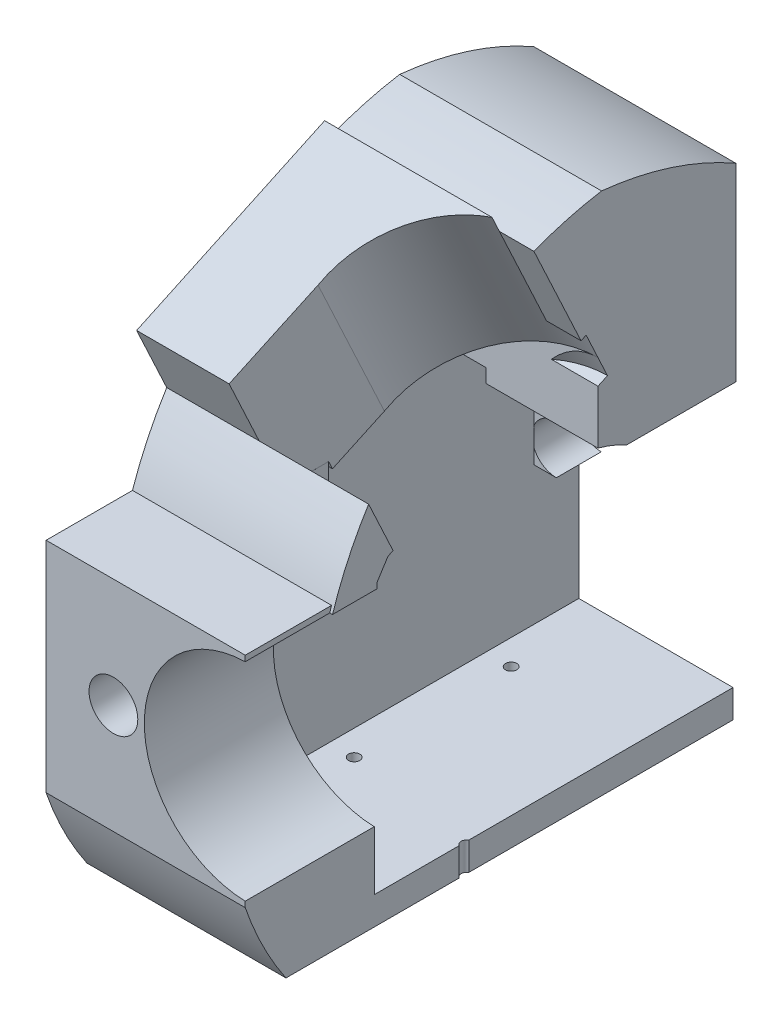
SolidWorks part; units mm, degrees
ref_plane "Front Plane" through (0, 0, 0) normal (0, 0, 1) x (1, 0, 0)
ref_plane "Top Plane" through (0, 0, 0) normal (0, 1, 0) x (1, 0, 0)
ref_plane "Right Plane" through (0, 0, 0) normal (1, 0, 0) x (0, 0, -1)
sketch "Sketch1" plane through (0, 0, 14.8713) normal (0, 0, 1) x (1, 0, 0)
  line L0 (17.8011, 32) -> (17.8011, 29.35)
  line L1 (13.8011, 20.65) -> (13.8011, 19.2554)
  line L2 (13.8011, 20.65) -> (13.8011, -4) construction
  line L3 (13.8011, 20.65) -> (17.8011, 20.65)
  arc A0 (17.8011, 32) -> (13.8011, 19.2554) centre (17.8011, 25) ccw
  arc A1 (22.3161, 30.3493) -> (17.8011, 32) centre (17.8011, 25) ccw construction
  arc A2 (17.8011, 29.35) -> (17.8011, 20.65) centre (17.8011, 25) ccw
extrude "Boss-Extrude1" add sketch "Sketch1" against normal up to surface (10.8581 mm away)
sketch "Sketch2" plane through (0, 0, -49.1287) normal (0, 0, -1) x (-1, 0, 0)
  line L0 (-13.8011, 19.2554) -> (-13.8011, 20.65)
  line L1 (-13.8011, 20.65) -> (-13.8011, -4) construction
  line L2 (-13.8011, 20.65) -> (-17.8011, 20.65)
  line L3 (-17.8011, 32) -> (-17.8011, 29.35)
  arc A0 (-13.8011, 19.2554) -> (-17.8011, 32) centre (-17.8011, 25) ccw
  arc A1 (-17.8011, 20.65) -> (-17.8011, 29.35) centre (-17.8011, 25) ccw
extrude "Boss-Extrude2" add sketch "Sketch2" against normal up to surface (8 mm away) separate body
sketch "Sketch3" plane through (0, 0, 14.8713) normal (0, 0, 1) x (1, 0, 0)
  line L0 (22.3161, 44.5) -> (61.3161, 44.5) construction
  line L1 (13.8011, 44.5) -> (5.8011, 44.5)
  line L3 (13.8011, -4) -> (5.8011, -4)
  line L4 (5.8011, 44.5) -> (5.8011, -4)
  line L5 (41.3161, -4) -> (13.8011, -4) construction
  line L6 (13.8011, 19.2554) -> (13.8011, -4)
  line L7 (22.3161, 30.3493) -> (22.3161, 44.5)
  line L8 (22.3161, 44.5) -> (13.8011, 44.5)
  arc A2 (22.3161, 30.3493) -> (17.8011, 32) centre (17.8011, 25) ccw construction
  arc A4 (22.3161, 30.3493) -> (17.8011, 32) centre (17.8011, 25) ccw
  arc A5 (17.8011, 32) -> (13.8011, 19.2554) centre (17.8011, 25) ccw construction
  arc A6 (17.8011, 32) -> (13.8011, 19.2554) centre (17.8011, 25) ccw
  dimension "D1" = 8
extrude "Boss-Extrude3" add sketch "Sketch3" against normal up to surface (10.8581 mm away)
sketch "Sketch4" plane through (0, 0, -49.1287) normal (0, 0, -1) x (-1, 0, 0)
  line L0 (-13.8011, 20.65) -> (-13.8011, -4) construction
  line L1 (-17.8011, 32) -> (-17.8011, 43.4634) construction
  line L2 (-13.8011, 19.2554) -> (-13.8011, -4)
  line L3 (-17.8011, 32) -> (-17.8011, 43.4634)
  line L4 (-17.8011, 43.4634) -> (-5.8011, 43.4634)
  line L5 (-5.8011, 44.5) -> (-5.8011, -4) construction
  line L6 (-5.8011, 43.4634) -> (-5.8011, -4)
  line L7 (-5.8011, -4) -> (-13.8011, -4)
  arc A0 (-13.8011, 19.2554) -> (-17.8011, 32) centre (-17.8011, 25) ccw construction
  arc A1 (-13.8011, 19.2554) -> (-17.8011, 32) centre (-17.8011, 25) ccw
extrude "Boss-Extrude4" add sketch "Sketch4" against normal up to surface (8 mm away)
sketch "Sketch5" plane through (0, 0, -41.1287) normal (0, 0, 1) x (1, 0, 0)
  line L2 (5.8011, 43.4634) -> (13.8011, 43.4634)
  line L3 (5.8011, 43.4634) -> (5.8011, -4)
  line L4 (5.8011, -4) -> (13.8011, -4)
  line L6 (13.8011, 43.4634) -> (13.8011, -4)
extrude "Boss-Extrude5" add sketch "Sketch5" along normal up to surface (45.1419 mm away) up to face at (14.7818, 23.8221, 4.0131)
sketch "Sketch6" plane through (0, 0, 14.8713) normal (0, 0, 1) x (1, 0, 0)
  line L0 (41.3161, 6.5068) -> (41.3161, -4)
  line L1 (5.8011, 44.5) -> (41.3161, 44.5)
  line L2 (5.8011, 44.5) -> (5.8011, -4)
  line L3 (5.8011, -4) -> (41.3161, -4)
  line L4 (41.3161, 44.5) -> (41.3161, 43.4932)
  circle A0 centre (41.8161, 25) radius 18.5 construction
  arc A1 (41.3161, 43.4932) -> (41.3161, 6.5068) centre (41.8161, 25) ccw
  arc A2 (17.8011, 20.65) -> (17.8011, 29.35) centre (17.8011, 25) ccw construction
  arc A3 (17.8011, 20.65) -> (17.8011, 29.35) centre (17.8011, 25) ccw
  arc A4 (17.8011, 29.35) -> (17.8011, 20.65) centre (17.8011, 25) ccw construction
  arc A5 (17.8011, 29.35) -> (17.8011, 20.65) centre (17.8011, 25) ccw
  point P8 (0, 0)
extrude "Boss-Extrude6" add sketch "Sketch6" along normal up to surface (23.0162 mm away)
sketch "Sketch7" plane through (41.8161, 0, 0) normal (-1, 0, 0) x (0, 0, 1)
  line L7 (16.3792, 57.333) -> (12.0176, 47.9794)
  line L8 (12.0176, 47.9794) -> (12.9239, 47.5568)
  line L9 (12.9239, 47.5568) -> (14.8713, 44.5)
  line L10 (14.8713, 44.5) -> (14.8713, 43.5)
  line L11 (14.8713, 43.5) -> (22.814, 43.5)
  line L13 (16.3792, 57.333) -> (12.0176, 47.9794)
  line L14 (12.0176, 47.9794) -> (12.9239, 47.5568)
  line L15 (12.9239, 47.5568) -> (14.8713, 44.5)
  line L16 (14.8713, 44.5) -> (14.8713, 43.5)
  line L17 (14.8713, 43.5) -> (22.814, 43.5)
  line L20 (-49.1287, 77.2293) -> (-49.1287, 43.4634)
  line L21 (-49.1287, 43.4634) -> (-24.5352, 43.4634)
  line L22 (-24.5352, 43.4634) -> (-24.5352, 59.5074)
  line L23 (-24.5352, 59.5074) -> (-22.4221, 64.0389)
  line L24 (-22.4221, 64.0389) -> (-21.5158, 63.6163)
  line L25 (-21.5158, 63.6163) -> (-13.1095, 81.6438)
  line L27 (-49.1287, 77.2293) -> (-49.1287, 43.4634)
  line L28 (-49.1287, 43.4634) -> (-29.5923, 43.4634)
  line L29 (-24.5352, 45.5265) -> (-24.5352, 59.5074)
  line L30 (-24.5352, 59.5074) -> (-22.4221, 64.0389)
  line L31 (-22.4221, 64.0389) -> (-21.5158, 63.6163)
  line L32 (-21.5158, 63.6163) -> (-13.1095, 81.6438)
  arc A0 (-24.5352, 45.5265) -> (-29.5923, 43.4634) centre (-19.1104, 25) ccw
  arc A1 (22.814, 43.5) -> (16.3792, 57.333) centre (-35.0418, 25) ccw
  arc A3 (-25.1762, 84.9351) -> (-49.1287, 77.2293) centre (-19.1104, 25) ccw
  arc A4 (-25.1762, 84.9351) -> (-49.1287, 77.2293) centre (-19.1104, 25) ccw
  arc A21 (22.814, 43.5) -> (16.3792, 57.333) centre (-35.0418, 25) ccw
  arc A23 (-13.1095, 81.6438) -> (-25.1762, 84.9351) centre (-35.0418, 25) ccw
  arc A24 (-13.1095, 81.6438) -> (-25.1762, 84.9351) centre (-35.0418, 25) ccw
  dimension "D1" = 0
  dimension "D2" = 0
extrude "Boss-Extrude7" add sketch "Sketch7" along normal up to surface (36.015 mm away) up to face at (5.8011, 27.9878, -2.4094)
sketch "Sketch8" plane through (5.8011, 0, 0) normal (-1, 0, 0) x (0, 0, 1)
  line L0 (14.8713, 44.5) -> (12.9239, 47.5568)
  line L1 (12.9239, 47.5568) -> (12.0176, 47.9794)
  line L2 (12.0176, 47.9794) -> (-24.5352, 47.9794)
  line L3 (-24.5352, 45.5265) -> (-24.5352, 59.5074) construction
  line L4 (-24.5352, 47.9794) -> (-24.5352, 45.5265)
  line L5 (-29.5923, 43.4634) -> (4.0131, 43.4634)
  line L6 (4.0131, 43.4634) -> (4.0131, 44.5)
  line L7 (4.0131, 44.5) -> (14.8713, 44.5)
  arc A0 (-24.5352, 45.5265) -> (-29.5923, 43.4634) centre (-19.1104, 25) ccw construction
  arc A1 (-24.5352, 45.5265) -> (-29.5923, 43.4634) centre (-19.1104, 25) ccw
extrude "Boss-Extrude8" add sketch "Sketch8" against normal up to surface (8 mm away) up to face at (13.8011, 23.4608, -18.9669)
sketch "Sketch9" plane through (13.8011, 0, 0) normal (1, 0, 0) x (0, 0, -1)
  line L0 (-4.0131, 44.5) -> (-4.0131, 47.9794)
  line L17 (-14.8713, 20.65) -> (-14.8713, -4)
  line L18 (-14.8713, -4) -> (49.1287, -4)
  line L19 (49.1287, -4) -> (49.1287, 20.65)
  line L20 (49.1287, 20.65) -> (41.1287, 20.65)
  line L21 (41.1287, 20.65) -> (41.1287, 23.2905)
  line L22 (41.1287, 23.2905) -> (41.1287, 26.7095)
  line L23 (41.1287, 26.7095) -> (41.1287, 43.4634)
  line L24 (41.1287, 43.4634) -> (29.5923, 43.4634)
  line L25 (24.5352, 45.5265) -> (24.5352, 47.9794)
  line L26 (24.5352, 47.9794) -> (-12.0176, 47.9794)
  line L27 (-12.0176, 47.9794) -> (-12.9239, 47.5568)
  line L28 (-12.9239, 47.5568) -> (-14.8713, 44.5)
  line L29 (-14.8713, 44.5) -> (-4.0131, 44.5)
  line L30 (-4.0131, 44.5) -> (-4.0131, 26.7095)
  line L31 (-4.0131, 26.7095) -> (-4.0131, 23.2905)
  line L32 (-4.0131, 23.2905) -> (-4.0131, 20.65)
  line L33 (-4.0131, 20.65) -> (-14.8713, 20.65)
  line L43 (-4.0131, 47.9794) -> (-12.0176, 47.9794)
  line L44 (-12.0176, 47.9794) -> (-12.9239, 47.5568)
  line L45 (-12.9239, 47.5568) -> (-14.8713, 44.5)
  line L46 (-14.8713, 44.5) -> (-4.0131, 44.5)
  arc A1 (29.5923, 43.4634) -> (24.5352, 45.5265) centre (19.1104, 25) ccw
  dimension "D1" = 0
extrude "Boss-Extrude9" add sketch "Sketch9" along normal up to surface (8.515 mm away)
sketch "Sketch11" plane through (13.8011, 0, 0) normal (1, 0, 0) x (0, 0, -1)
  line L0 (24.5352, 47.9794) -> (24.5352, 45.5265)
  line L1 (41.1287, 43.4634) -> (41.1287, 47.9794)
  line L2 (52.7432, 45.6866) -> (52.5609, 45.6856)
  line L3 (41.1287, 47.9794) -> (24.5352, 47.9794)
  line L4 (49.1287, 43.4634) -> (29.5923, 43.4634) construction
  line L5 (41.1287, 43.4634) -> (29.5923, 43.4634)
  arc A0 (29.5923, 43.4634) -> (24.5352, 45.5265) centre (19.1104, 25) ccw construction
  arc A1 (29.5923, 43.4634) -> (24.5352, 45.5265) centre (19.1104, 25) ccw
extrude "Cut-Extrude4" cut sketch "Sketch11" along normal blind 8 contours A1 L0 L3 L1 L5
sketch "Sketch14" plane through (0, 39.4814, 18.4105) normal (0, -0.9063, -0.4226) x (1, 0, 0)
  line L2 (22.3161, -16.6399) -> (13.8011, -16.6399)
  line L3 (13.8011, -16.6399) -> (13.8011, -44.7208)
  line L4 (13.8011, -44.7208) -> (31.9764, -44.7208)
  line L5 (22.3161, -16.6399) -> (22.3448, -26.8287)
  arc A0 (22.3448, -26.8287) -> (61.3161, -27.8854) centre (41.8161, -27.8854) ccw construction
  arc A1 (22.3448, -26.8287) -> (31.9764, -44.7208) centre (41.8161, -27.8854) ccw
extrude "Boss-Extrude19" add sketch "Sketch14" against normal up to surface (5 mm away) separate body
sketch "Sketch15" plane through (0, 20.0259, -42.9457) normal (0, -0.4226, 0.9063) x (1, 0, 0)
  line L4 (5.8011, 48.563) -> (5.8011, 43.563)
  line L5 (5.8011, 43.563) -> (41.8161, 43.563)
  line L6 (41.8161, 43.563) -> (41.8161, 48.563)
  line L7 (41.8161, 48.563) -> (5.8011, 48.563)
  line L8 (5.8011, 48.563) -> (5.8011, 43.563)
  line L9 (5.8011, 43.563) -> (41.8161, 43.563)
  line L10 (41.8161, 43.563) -> (41.8161, 48.563)
  line L11 (41.8161, 48.563) -> (5.8011, 48.563)
  dimension "D1" = 0
extrude "Boss-Extrude21" add sketch "Sketch15" along normal up to surface (2.6646 mm away) separate body up to face at (22.8888, 60.647, -21.0637)
sketch "Sketch16" plane through (5.8011, 0, 0) normal (-1, 0, 0) x (0, 0, 1)
  line L0 (12.0176, 47.9794) -> (-24.5352, 47.9794) construction
  line L1 (-24.5352, 47.9794) -> (-24.5352, 59.5074) construction
  line L2 (-22.1203, 58.3813) -> (-24.5352, 59.5074) construction
  line L3 (3.3297, 46.5137) -> (-22.1203, 58.3813) construction
  line L4 (0.1865, 47.9794) -> (-24.5352, 47.9794)
  line L5 (-24.5352, 47.9794) -> (-24.5352, 59.5074)
  line L6 (-22.1203, 58.3813) -> (-24.5352, 59.5074)
  line L7 (0.1865, 47.9794) -> (-22.1203, 58.3813)
extrude "Boss-Extrude23" add sketch "Sketch16" against normal up to surface (8 mm away) separate body up to face at (13.8011, 54.7133, -8.3388)
sketch "Sketch17" plane through (5.8011, 0, 0) normal (-1, 0, 0) x (0, 0, 1)
  line L0 (-22.1203, 58.3813) -> (0.1865, 47.9794)
  line L1 (0.1865, 47.9794) -> (12.0176, 47.9794)
  line L2 (12.0176, 47.9794) -> (-20.0072, 62.9128)
  line L3 (-20.0072, 62.9128) -> (-22.1203, 58.3813)
extrude "Boss-Extrude25" add sketch "Sketch17" against normal up to surface (8 mm away) separate body up to face at (13.8011, 54.7133, -8.3388)
sketch "Sketch18" plane through (13.8011, 0, 0) normal (1, 0, 0) x (0, 0, -1)
  line L0 (-5.4428, 51.0453) -> (-12.0176, 47.9794)
  line L1 (-12.0176, 47.9794) -> (-4.0131, 47.9794)
  line L2 (-4.0131, 47.9794) -> (-5.4428, 51.0453)
extrude "Boss-Extrude26" add sketch "Sketch18" along normal up to surface (8.4946 mm away) up to face at (22.3305, 50.9325, -0.2309)
sketch "Sketch19" plane through (0, 44.013, 20.5236) normal (0, 0.9063, 0.4226) x (1, 0, 0)
  line L0 (22.3448, 26.8287) -> (61.3161, 27.8854)
  arc A0 (61.3161, 27.8854) -> (22.3448, 26.8287) centre (41.8161, 27.8854) ccw construction
  arc A1 (61.3161, 27.8854) -> (22.3448, 26.8287) centre (41.8161, 27.8854) ccw
extrude "Cut-Extrude5" cut sketch "Sketch19" against normal blind 9
sketch "Sketch20" plane through (0, 44.013, 20.5236) normal (0, 0.9063, 0.4226) x (1, 0, 0)
  line L0 (5.8011, 46.3854) -> (5.8011, 9.3854)
  line L1 (5.8011, 9.3854) -> (22.2957, 9.3854)
  line L2 (22.2957, 9.3854) -> (22.3448, 26.8287)
  line L3 (5.8011, 46.3854) -> (35.6517, 46.3854)
  arc A0 (61.3161, 27.8854) -> (22.3448, 26.8287) centre (41.8161, 27.8854) ccw construction
  arc A1 (35.6517, 46.3854) -> (22.3448, 26.8287) centre (41.8161, 27.8854) ccw
  point P6 (22.344, 26.5453)
extrude "Boss-Extrude27" add sketch "Sketch20" along normal up to surface (23.0162 mm away)
sketch "Sketch21" plane through (0, 44.013, 20.5236) normal (0, 0.9063, 0.4226) x (1, 0, 0)
  line L3 (41.8161, 9.3854) -> (22.2957, 9.3854)
  line L4 (22.2957, 9.3854) -> (22.3448, 26.8287)
  line L5 (35.6517, 46.3854) -> (41.8161, 46.3854)
  arc A4 (22.3448, 26.8287) -> (35.6517, 46.3854) centre (41.8161, 27.8854) cw
  arc A5 (41.8161, 9.3854) -> (41.8161, 46.3854) centre (41.8161, 27.8854) cw
extrude "Boss-Extrude28" add sketch "Sketch21" along normal up to surface (23.0162 mm away) rebuild error yes
sketch "Sketch22" plane through (0, -4, 0) normal (0, -1, 0) x (1, 0, 0)
  line L1 (41.3161, 33.6911) -> (5.8011, 33.6911)
  line L2 (41.3161, 33.6911) -> (41.3161, -49.1287)
  line L3 (41.3161, -49.1287) -> (5.8011, -49.1287)
  line L4 (5.8011, 33.6911) -> (5.8011, -49.1287)
  point P6 (0, 0)
extrude "Boss-Extrude29" add sketch "Sketch22" along normal up to surface (5 mm away)
ref_plane "Plane1" through (13.8011, 40.5048, -22.0418) normal (0, -1, 0) x (-1, 0, 0)
sketch "Sketch24" plane through (5.8011, 0, 0) normal (-1, 0, 0) x (0, 0, 1)
  arc A1 (-25.1762, 84.9351) -> (-49.1287, 77.2293) centre (-19.1104, 25) ccw construction
  circle A2 centre (-19.1104, 25) radius 60.2412
  circle A3 centre (-19.1104, 25) radius 106.9512
extrude "Cut-Extrude6" cut sketch "Sketch24" against normal through all
sketch "Sketch25" plane through (0, -9, 0) normal (0, -1, 0) x (1, 0, 0)
  circle A0 centre (41.8161, -1.1287) radius 1
  arc A1 (41.3161, -1.9948) -> (41.3161, -0.2627) centre (41.8161, -1.1287) ccw construction
  circle A2 centre (18.3011, -4.5578) radius 1
  circle A3 centre (18.3011, -32.5578) radius 1
extrude "Cut-Extrude7" cut sketch "Sketch25" against normal blind 10
